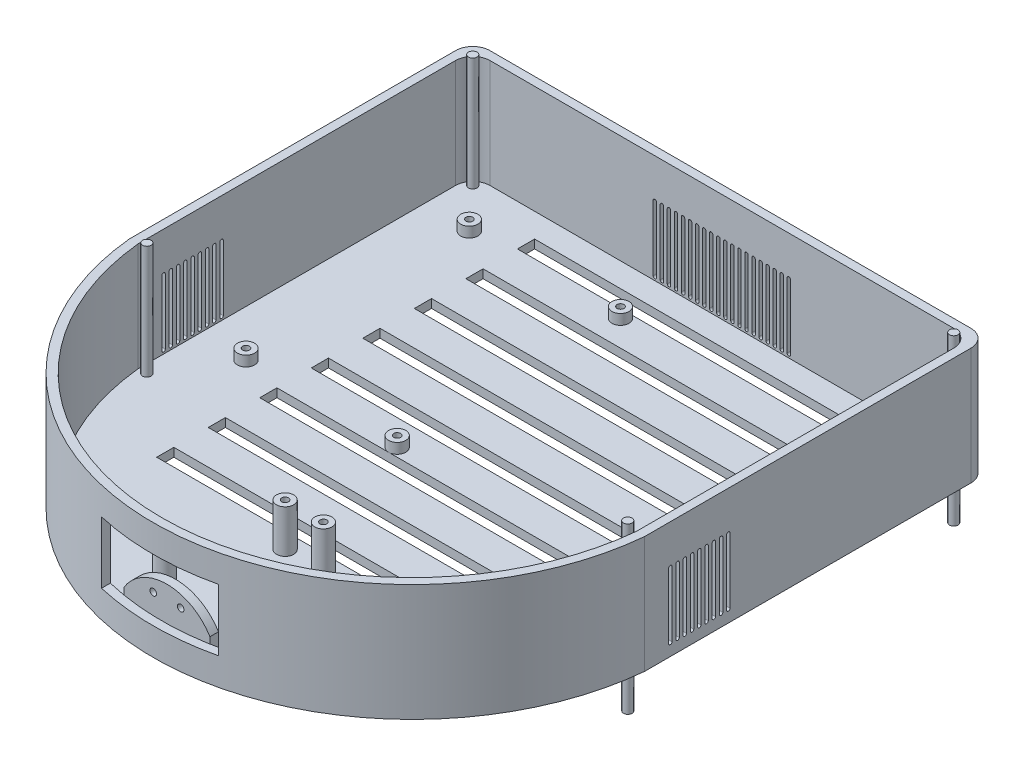
SolidWorks part; units mm, degrees
material "6063-O"
ref_plane "Front Plane" through (0, 0, 0) normal (0, 0, 1) x (1, 0, 0)
ref_plane "Top Plane" through (0, 0, 0) normal (0, 1, 0) x (1, 0, 0)
ref_plane "Right Plane" through (0, 0, 0) normal (1, 0, 0) x (0, 0, -1)
sketch "Sketch1" plane through (0, 0, 0) normal (0, 1, 0) x (1, 0, 0)
  line L1 (-190.5, -213.36) -> (190.5, -213.36)
  line L2 (-190.5, -213.36) -> (-190.5, 213.36)
  line L3 (-190.5, 213.36) -> (190.5, 213.36)
  line L4 (190.5, -213.36) -> (190.5, 213.36)
  line L5 (-190.5, -213.36) -> (190.5, 213.36) construction
  line L6 (-190.5, 213.36) -> (190.5, -213.36) construction
  arc A0 (190.5, -40.64) -> (-190.5, -40.64) centre (0, -21.9449) cw
  point P0 (0, 0)
  dimension "D1" = 381
  dimension "D2" = 426.72
  dimension "D3" = 254
extrude "Boss-Extrude1" add sketch "Sketch1" along normal blind 86.36 contours L4 L3 L2 L1 region at (0, 0, -17.9529)
shell "Shell1" thickness 6.35 removed face at (0, 86.36, -43.18)
fillet "Fillet2" radius 12.7 4 edges at (-190.5, 43.18, -213.36) (190.5, 43.18, -213.36) (184.15, 46.355, -207.01) (-184.15, 46.355, -207.01)
sketch "Sketch3" plane through (0, 6.35, 0) normal (0, 1, 0) x (1, 0, 0)
  line L0 (-177.8, 200.66) -> (-177.8, -40.3265) construction
  circle A2 centre (-177.8, 200.66) radius 7.62
  arc A5 (-177.8, 213.36) -> (-190.5, 200.66) centre (-177.8, 200.66) ccw construction
  circle A6 centre (-177.8, -40.3265) radius 7.62
  circle A8 centre (-177.8, 200.66) radius 3.175
  circle A9 centre (-177.8, -40.3265) radius 3.175
  dimension "D1" = 15.24
  dimension "D2" = 6.35
extrude "Boss-Extrude2" add sketch "Sketch3" against normal blind 38.1 and the other way blind 83.82 contours A9 | A8
mirror "Mirror1" about plane through (0, 0, 0) normal (1, 0, 0) of "Boss-Extrude2"
sketch "Sketch8" plane through (0, 0, -213.36) normal (0, 0, -1) x (-1, 0, 0)
  line L1 (177.8, 0) -> (-177.8, 0) construction
  line L2 (-50.8, 58.42) -> (50.8, 58.42)
  line L3 (-50.8, 58.42) -> (-50.8, 7.62)
  line L4 (-50.8, 7.62) -> (50.8, 7.62)
  line L5 (50.8, 58.42) -> (50.8, 7.62)
  line L6 (-50.8, 58.42) -> (50.8, 7.62) construction
  line L7 (-50.8, 7.62) -> (50.8, 58.42) construction
  line L8 (-49.53, 57.15) -> (-49.53, 8.89) construction
  line L9 (-48.26, 57.15) -> (-48.26, 8.89)
  line L10 (-50.8, 57.15) -> (-50.8, 8.89)
  line L11 (-45.5863, 57.15) -> (-45.5863, 8.89)
  line L12 (-43.0463, 57.15) -> (-43.0463, 8.89)
  line L13 (-44.3163, 57.15) -> (-44.3163, 8.89) construction
  line L14 (-40.3726, 57.15) -> (-40.3726, 8.89)
  line L15 (-37.8326, 57.15) -> (-37.8326, 8.89)
  line L16 (-39.1026, 57.15) -> (-39.1026, 8.89) construction
  line L17 (-35.1589, 57.15) -> (-35.1589, 8.89)
  line L18 (-32.6189, 57.15) -> (-32.6189, 8.89)
  line L19 (-33.8889, 57.15) -> (-33.8889, 8.89) construction
  line L20 (-29.9453, 57.15) -> (-29.9453, 8.89)
  line L21 (-27.4053, 57.15) -> (-27.4053, 8.89)
  line L22 (-28.6753, 57.15) -> (-28.6753, 8.89) construction
  line L23 (-24.7316, 57.15) -> (-24.7316, 8.89)
  line L24 (-22.1916, 57.15) -> (-22.1916, 8.89)
  line L25 (-23.4616, 57.15) -> (-23.4616, 8.89) construction
  line L26 (-19.5179, 57.15) -> (-19.5179, 8.89)
  line L27 (-16.9779, 57.15) -> (-16.9779, 8.89)
  line L28 (-18.2479, 57.15) -> (-18.2479, 8.89) construction
  line L29 (-14.3042, 57.15) -> (-14.3042, 8.89)
  line L30 (-11.7642, 57.15) -> (-11.7642, 8.89)
  line L31 (-13.0342, 57.15) -> (-13.0342, 8.89) construction
  line L32 (-9.0905, 57.15) -> (-9.0905, 8.89)
  line L33 (-6.5505, 57.15) -> (-6.5505, 8.89)
  line L34 (-7.8205, 57.15) -> (-7.8205, 8.89) construction
  line L35 (-3.8768, 57.15) -> (-3.8768, 8.89)
  line L36 (-1.3368, 57.15) -> (-1.3368, 8.89)
  line L37 (-2.6068, 57.15) -> (-2.6068, 8.89) construction
  line L38 (1.3368, 57.15) -> (1.3368, 8.89)
  line L39 (3.8768, 57.15) -> (3.8768, 8.89)
  line L40 (2.6068, 57.15) -> (2.6068, 8.89) construction
  line L41 (6.5505, 57.15) -> (6.5505, 8.89)
  line L42 (9.0905, 57.15) -> (9.0905, 8.89)
  line L43 (7.8205, 57.15) -> (7.8205, 8.89) construction
  line L44 (11.7642, 57.15) -> (11.7642, 8.89)
  line L45 (14.3042, 57.15) -> (14.3042, 8.89)
  line L46 (13.0342, 57.15) -> (13.0342, 8.89) construction
  line L47 (16.9779, 57.15) -> (16.9779, 8.89)
  line L48 (19.5179, 57.15) -> (19.5179, 8.89)
  line L49 (18.2479, 57.15) -> (18.2479, 8.89) construction
  line L50 (22.1916, 57.15) -> (22.1916, 8.89)
  line L51 (24.7316, 57.15) -> (24.7316, 8.89)
  line L52 (23.4616, 57.15) -> (23.4616, 8.89) construction
  line L53 (27.4053, 57.15) -> (27.4053, 8.89)
  line L54 (29.9453, 57.15) -> (29.9453, 8.89)
  line L55 (28.6753, 57.15) -> (28.6753, 8.89) construction
  line L56 (32.6189, 57.15) -> (32.6189, 8.89)
  line L57 (35.1589, 57.15) -> (35.1589, 8.89)
  line L58 (33.8889, 57.15) -> (33.8889, 8.89) construction
  line L59 (37.8326, 57.15) -> (37.8326, 8.89)
  line L60 (40.3726, 57.15) -> (40.3726, 8.89)
  line L61 (39.1026, 57.15) -> (39.1026, 8.89) construction
  line L62 (43.0463, 57.15) -> (43.0463, 8.89)
  line L63 (45.5863, 57.15) -> (45.5863, 8.89)
  line L64 (44.3163, 57.15) -> (44.3163, 8.89) construction
  line L65 (48.26, 57.15) -> (48.26, 8.89)
  line L66 (50.8, 57.15) -> (50.8, 8.89)
  line L67 (49.53, 57.15) -> (49.53, 8.89) construction
  arc A12 (-48.26, 57.15) -> (-50.8, 57.15) centre (-49.53, 57.15) ccw
  arc A13 (-50.8, 8.89) -> (-48.26, 8.89) centre (-49.53, 8.89) ccw
  arc A14 (-43.0463, 57.15) -> (-45.5863, 57.15) centre (-44.3163, 57.15) ccw
  arc A15 (-45.5863, 8.89) -> (-43.0463, 8.89) centre (-44.3163, 8.89) ccw
  arc A16 (-37.8326, 57.15) -> (-40.3726, 57.15) centre (-39.1026, 57.15) ccw
  arc A17 (-40.3726, 8.89) -> (-37.8326, 8.89) centre (-39.1026, 8.89) ccw
  arc A18 (-32.6189, 57.15) -> (-35.1589, 57.15) centre (-33.8889, 57.15) ccw
  arc A19 (-35.1589, 8.89) -> (-32.6189, 8.89) centre (-33.8889, 8.89) ccw
  arc A20 (-27.4053, 57.15) -> (-29.9453, 57.15) centre (-28.6753, 57.15) ccw
  arc A21 (-29.9453, 8.89) -> (-27.4053, 8.89) centre (-28.6753, 8.89) ccw
  arc A22 (-22.1916, 57.15) -> (-24.7316, 57.15) centre (-23.4616, 57.15) ccw
  arc A23 (-24.7316, 8.89) -> (-22.1916, 8.89) centre (-23.4616, 8.89) ccw
  arc A24 (-16.9779, 57.15) -> (-19.5179, 57.15) centre (-18.2479, 57.15) ccw
  arc A25 (-19.5179, 8.89) -> (-16.9779, 8.89) centre (-18.2479, 8.89) ccw
  arc A26 (-11.7642, 57.15) -> (-14.3042, 57.15) centre (-13.0342, 57.15) ccw
  arc A27 (-14.3042, 8.89) -> (-11.7642, 8.89) centre (-13.0342, 8.89) ccw
  arc A28 (-6.5505, 57.15) -> (-9.0905, 57.15) centre (-7.8205, 57.15) ccw
  arc A29 (-9.0905, 8.89) -> (-6.5505, 8.89) centre (-7.8205, 8.89) ccw
  arc A30 (-1.3368, 57.15) -> (-3.8768, 57.15) centre (-2.6068, 57.15) ccw
  arc A31 (-3.8768, 8.89) -> (-1.3368, 8.89) centre (-2.6068, 8.89) ccw
  arc A32 (3.8768, 57.15) -> (1.3368, 57.15) centre (2.6068, 57.15) ccw
  arc A33 (1.3368, 8.89) -> (3.8768, 8.89) centre (2.6068, 8.89) ccw
  arc A34 (9.0905, 57.15) -> (6.5505, 57.15) centre (7.8205, 57.15) ccw
  arc A35 (6.5505, 8.89) -> (9.0905, 8.89) centre (7.8205, 8.89) ccw
  arc A36 (14.3042, 57.15) -> (11.7642, 57.15) centre (13.0342, 57.15) ccw
  arc A37 (11.7642, 8.89) -> (14.3042, 8.89) centre (13.0342, 8.89) ccw
  arc A38 (19.5179, 57.15) -> (16.9779, 57.15) centre (18.2479, 57.15) ccw
  arc A39 (16.9779, 8.89) -> (19.5179, 8.89) centre (18.2479, 8.89) ccw
  arc A40 (24.7316, 57.15) -> (22.1916, 57.15) centre (23.4616, 57.15) ccw
  arc A41 (22.1916, 8.89) -> (24.7316, 8.89) centre (23.4616, 8.89) ccw
  arc A42 (29.9453, 57.15) -> (27.4053, 57.15) centre (28.6753, 57.15) ccw
  arc A43 (27.4053, 8.89) -> (29.9453, 8.89) centre (28.6753, 8.89) ccw
  arc A44 (35.1589, 57.15) -> (32.6189, 57.15) centre (33.8889, 57.15) ccw
  arc A45 (32.6189, 8.89) -> (35.1589, 8.89) centre (33.8889, 8.89) ccw
  arc A46 (40.3726, 57.15) -> (37.8326, 57.15) centre (39.1026, 57.15) ccw
  arc A47 (37.8326, 8.89) -> (40.3726, 8.89) centre (39.1026, 8.89) ccw
  arc A48 (45.5863, 57.15) -> (43.0463, 57.15) centre (44.3163, 57.15) ccw
  arc A49 (43.0463, 8.89) -> (45.5863, 8.89) centre (44.3163, 8.89) ccw
  arc A50 (50.8, 57.15) -> (48.26, 57.15) centre (49.53, 57.15) ccw
  arc A51 (48.26, 8.89) -> (50.8, 8.89) centre (49.53, 8.89) ccw
  point P0 (0, 33.02)
  point P12 (-49.53, 33.02)
  point P21 (-44.3163, 33.02)
  point P28 (-39.1026, 33.02)
  point P36 (-33.8889, 33.02)
  point P43 (-28.6753, 33.02)
  point P50 (-23.4616, 33.02)
  point P57 (-18.2479, 33.02)
  point P64 (-13.0342, 33.02)
  point P71 (-7.8205, 33.02)
  point P78 (-2.6068, 33.02)
  point P85 (2.6068, 33.02)
  point P92 (7.8205, 33.02)
  point P99 (13.0342, 33.02)
  point P106 (18.2479, 33.02)
  point P113 (23.4616, 33.02)
  point P120 (28.6753, 33.02)
  point P127 (33.8889, 33.02)
  point P134 (39.1026, 33.02)
  point P141 (44.3163, 33.02)
  point P148 (49.53, 33.02)
  dimension "D1" = 101.6
  dimension "D2" = 50.8
  dimension "D3" = 7.62
  dimension "D4" = 2.54
  dimension "D5" = 20
extrude "Cut-Extrude4" cut sketch "Sketch8" against normal up to surface (6.35 mm away) contours L10 A13 L9 A12 | L12 A15 L11 A14 | L15 A17 L14 A16 | L18 A19 L17 A18 | L21 A21 L20 A20 | L24 A23 L23 A22 | L27 A25 L26 A24 | L30 A27 L29 A26 | L33 A29 L32 A28 | L36 A31 L35 A30 | L39 A33 L38 A32 | L42 A35 L41 A34 | L45 A37 L44 A36 | L48 A39 L47 A38 | L51 A41 L50 A40 | L54 A43 L53 A42 | L57 A45 L56 A44 | L60 A47 L59 A46 | L63 A49 L62 A48 | L66 A51 L65 A50 up to face at (0, 46.355, -207.01)
sketch "Sketch10" plane through (190.5, 0, 0) normal (1, 0, 0) x (0, 0, -1)
  line L0 (-22.86, 58.42) -> (27.94, 58.42)
  line L1 (-22.86, 58.42) -> (-22.86, 7.62)
  line L2 (-22.86, 7.62) -> (27.94, 7.62)
  line L3 (27.94, 58.42) -> (27.94, 7.62)
  line L4 (-22.86, 58.42) -> (27.94, 7.62) construction
  line L5 (-22.86, 7.62) -> (27.94, 58.42) construction
  line L6 (-40.64, 86.36) -> (-40.64, 0) construction
  line L11 (-40.64, 0) -> (200.66, 0) construction
  line L14 (-21.59, 57.15) -> (-21.59, 8.89) construction
  line L17 (-20.32, 57.15) -> (-20.32, 8.89)
  line L20 (-22.86, 57.15) -> (-22.86, 8.89)
  line L23 (-17.4978, 57.15) -> (-17.4978, 8.89)
  line L26 (-14.9578, 57.15) -> (-14.9578, 8.89)
  line L29 (-16.2278, 57.15) -> (-16.2278, 8.89) construction
  line L32 (-12.1356, 57.15) -> (-12.1356, 8.89)
  line L35 (-9.5956, 57.15) -> (-9.5956, 8.89)
  line L38 (-10.8656, 57.15) -> (-10.8656, 8.89) construction
  line L41 (-6.7733, 57.15) -> (-6.7733, 8.89)
  line L44 (-4.2333, 57.15) -> (-4.2333, 8.89)
  line L47 (-5.5033, 57.15) -> (-5.5033, 8.89) construction
  line L50 (-1.4111, 57.15) -> (-1.4111, 8.89)
  line L53 (1.1289, 57.15) -> (1.1289, 8.89)
  line L56 (-0.1411, 57.15) -> (-0.1411, 8.89) construction
  line L59 (3.9511, 57.15) -> (3.9511, 8.89)
  line L62 (6.4911, 57.15) -> (6.4911, 8.89)
  line L65 (5.2211, 57.15) -> (5.2211, 8.89) construction
  line L66 (9.3133, 57.15) -> (9.3133, 8.89)
  line L67 (11.8533, 57.15) -> (11.8533, 8.89)
  line L68 (10.5833, 57.15) -> (10.5833, 8.89) construction
  line L69 (14.6756, 57.15) -> (14.6756, 8.89)
  line L70 (17.2156, 57.15) -> (17.2156, 8.89)
  line L71 (15.9456, 57.15) -> (15.9456, 8.89) construction
  line L72 (20.0378, 57.15) -> (20.0378, 8.89)
  line L73 (22.5778, 57.15) -> (22.5778, 8.89)
  line L74 (21.3078, 57.15) -> (21.3078, 8.89) construction
  line L75 (25.4, 57.15) -> (25.4, 8.89)
  line L76 (27.94, 57.15) -> (27.94, 8.89)
  line L77 (26.67, 57.15) -> (26.67, 8.89) construction
  arc A40 (-20.32, 57.15) -> (-22.86, 57.15) centre (-21.59, 57.15) ccw
  arc A41 (-22.86, 8.89) -> (-20.32, 8.89) centre (-21.59, 8.89) ccw
  arc A42 (-14.9578, 57.15) -> (-17.4978, 57.15) centre (-16.2278, 57.15) ccw
  arc A43 (-17.4978, 8.89) -> (-14.9578, 8.89) centre (-16.2278, 8.89) ccw
  arc A44 (-9.5956, 57.15) -> (-12.1356, 57.15) centre (-10.8656, 57.15) ccw
  arc A45 (-12.1356, 8.89) -> (-9.5956, 8.89) centre (-10.8656, 8.89) ccw
  arc A46 (-4.2333, 57.15) -> (-6.7733, 57.15) centre (-5.5033, 57.15) ccw
  arc A47 (-6.7733, 8.89) -> (-4.2333, 8.89) centre (-5.5033, 8.89) ccw
  arc A48 (1.1289, 57.15) -> (-1.4111, 57.15) centre (-0.1411, 57.15) ccw
  arc A49 (-1.4111, 8.89) -> (1.1289, 8.89) centre (-0.1411, 8.89) ccw
  arc A50 (6.4911, 57.15) -> (3.9511, 57.15) centre (5.2211, 57.15) ccw
  arc A51 (3.9511, 8.89) -> (6.4911, 8.89) centre (5.2211, 8.89) ccw
  arc A52 (11.8533, 57.15) -> (9.3133, 57.15) centre (10.5833, 57.15) ccw
  arc A53 (9.3133, 8.89) -> (11.8533, 8.89) centre (10.5833, 8.89) ccw
  arc A54 (17.2156, 57.15) -> (14.6756, 57.15) centre (15.9456, 57.15) ccw
  arc A55 (14.6756, 8.89) -> (17.2156, 8.89) centre (15.9456, 8.89) ccw
  arc A56 (22.5778, 57.15) -> (20.0378, 57.15) centre (21.3078, 57.15) ccw
  arc A57 (20.0378, 8.89) -> (22.5778, 8.89) centre (21.3078, 8.89) ccw
  arc A58 (27.94, 57.15) -> (25.4, 57.15) centre (26.67, 57.15) ccw
  arc A59 (25.4, 8.89) -> (27.94, 8.89) centre (26.67, 8.89) ccw
  point P0 (2.54, 33.02)
  point P9 (-21.59, 33.02)
  point P20 (-16.2278, 33.02)
  point P27 (-10.8656, 33.02)
  point P34 (-5.5033, 33.02)
  point P41 (-0.1411, 33.02)
  point P48 (5.2211, 33.02)
  point P55 (10.5833, 33.02)
  point P62 (15.9456, 33.02)
  point P69 (21.3078, 33.02)
  point P76 (26.67, 33.02)
  dimension "D1" = 7.62
  dimension "D2" = 50.8
  dimension "D3" = 50.8
  dimension "D4" = 17.78
  dimension "D5" = 2.54
  dimension "D6" = 10
extrude "Cut-Extrude5" cut sketch "Sketch10" against normal up to surface (6.35 mm away) contours L1 A41 L17 A40 | L23 A43 L26 A42 | L41 A47 L44 A46 | L59 A51 L62 A50 | L66 A53 L67 A52 | L69 A55 L70 A54 | L72 A57 L73 A56 | L32 A45 L35 A44 | L53 A49 L50 A48 region at (190.5, 33.02, 21.59) region at (190.5, 33.02, 16.2278) region at (190.5, 33.02, 5.5033) region at (190.5, 33.02, -5.2211) region at (190.5, 33.02, -10.5833) region at (190.5, 33.02, -15.9456) region at (190.5, 33.02, -21.3078) up to face at (184.15, 46.355, -76.9917)
mirror "Mirror2" about plane through (0, 0, 0) normal (1, 0, 0) of "Cut-Extrude5"
sketch "Sketch11" plane through (0, 6.35, 0) normal (0, 1, 0) x (1, 0, 0)
  line L0 (-171.45, 207.01) -> (171.45, 207.01) construction
  line L1 (-156.21, 176.53) -> (-31.75, 176.53)
  line L2 (-156.21, 176.53) -> (-156.21, -1.27)
  line L3 (-156.21, -1.27) -> (-31.75, -1.27)
  line L4 (-31.75, 176.53) -> (-31.75, -1.27)
  line L5 (-156.21, 176.53) -> (-31.75, -1.27) construction
  line L6 (-156.21, -1.27) -> (-31.75, 176.53) construction
  line L7 (184.15, -40.3265) -> (184.15, 194.31) construction
  circle A0 centre (-149.86, 170.18) radius 6.35
  circle A1 centre (-149.86, 5.08) radius 6.35
  circle A2 centre (-149.86, 170.18) radius 2.54
  circle A3 centre (-149.86, 5.08) radius 2.54
  circle A4 centre (-38.1, 170.18) radius 6.35
  circle A5 centre (-38.1, 170.18) radius 2.54
  circle A6 centre (-38.1, 5.08) radius 6.35
  circle A7 centre (-38.1, 5.08) radius 2.54
  point P0 (-93.98, 87.63)
  dimension "D4" = 12.7
  dimension "D5" = 5.08
  dimension "D1" = 124.46
  dimension "D2" = 177.8
  dimension "D3" = 30.48
  dimension "D6" = 215.9
extrude "Boss-Extrude3" add sketch "Sketch11" along normal blind 7.62 contours A0 A2 | A1 A3 | A4 | A6 | A7 | A5 region at (-145.4969, 6.35, -174.5431) region at (-149.86, 6.35, -11.2504)
sketch "Sketch12" plane through (0, 6.35, 0) normal (0, 1, 0) x (1, 0, 0)
  line L0 (-171.45, 207.01) -> (171.45, 207.01) construction
  line L5 (120.65, 189.23) -> (-120.65, 189.23)
  line L6 (120.65, 189.23) -> (120.65, 176.53)
  line L7 (120.65, 176.53) -> (-120.65, 176.53)
  line L8 (-120.65, 189.23) -> (-120.65, 176.53)
  line L9 (120.65, 189.23) -> (-120.65, 176.53) construction
  line L10 (120.65, 176.53) -> (-120.65, 189.23) construction
  point P0 (0, 182.88)
  dimension "D1" = 12.7
  dimension "D2" = 241.3
  dimension "D3" = 17.78
extrude "Cut-Extrude6" cut sketch "Sketch12" against normal up to surface (6.35 mm away) up to face at (177.8, 0, -197.485)
pattern_linear "LPattern1" count 8 spacing 38.1 along (0, 0, 1) of "Cut-Extrude6"
ref_plane "Plane1" through (0, 0, 213.36) normal (0, 0, -1) x (-1, 0, 0)
sketch "Sketch13" plane through (0, 0, 213.36) normal (0, 0, -1) x (-1, 0, 0)
  line L1 (43.18, 66.04) -> (-43.18, 66.04)
  line L2 (43.18, 66.04) -> (43.18, 20.32)
  line L3 (43.18, 20.32) -> (-43.18, 20.32)
  line L4 (-43.18, 66.04) -> (-43.18, 20.32)
  line L5 (43.18, 66.04) -> (-43.18, 20.32) construction
  line L6 (43.18, 20.32) -> (-43.18, 66.04) construction
  line L8 (-190.5, 86.36) -> (-190.5, 0) construction
  point P0 (0, 43.18)
  point P14 (-190.5, 43.18)
  dimension "D1" = 86.36
  dimension "D2" = 45.72
extrude "Cut-Extrude7" cut sketch "Sketch13" along normal up to surface (11.4579 mm away) up to face at (0, 46.355, 123.6683)
sketch "Sketch14" plane through (0, 6.35, 0) normal (0, 1, 0) x (1, 0, 0)
  line L1 (-31.75, -196.85) -> (31.75, -196.85)
  line L2 (-31.75, -196.85) -> (-31.75, -203.2)
  line L3 (-31.75, -203.2) -> (31.75, -203.2)
  line L4 (31.75, -196.85) -> (31.75, -203.2)
  line L5 (-31.75, -196.85) -> (31.75, -203.2) construction
  line L6 (-31.75, -203.2) -> (31.75, -196.85) construction
  point P0 (0, -200.025)
  dimension "D1" = 6.35
  dimension "D2" = 63.5
  dimension "D3" = 196.85
extrude "Boss-Extrude4" add sketch "Sketch14" along normal blind 35.56
sketch "Sketch15" plane through (0, 0, 203.2) normal (0, 0, 1) x (1, 0, 0)
  line L1 (-31.75, 41.91) -> (31.75, 41.91) construction
  line L2 (-31.75, 41.91) -> (-31.75, 6.35) construction
  line L3 (-31.75, 24.13) -> (-31.75, 6.35)
  line L4 (-31.75, 6.35) -> (31.75, 6.35)
  line L5 (31.75, 6.35) -> (31.75, 24.13)
  line L6 (10.16, 31.75) -> (-10.16, 31.75) construction
  line L7 (-31.75, 24.13) -> (-31.75, 41.91)
  line L8 (-31.75, 41.91) -> (31.75, 41.91)
  line L9 (31.75, 41.91) -> (31.75, 24.13)
  arc A0 (-31.75, 24.13) -> (31.75, 24.13) centre (0, 4.6718) cw
  circle A1 centre (-10.16, 31.75) radius 2.413
  circle A2 centre (10.16, 31.75) radius 2.413
  point P11 (0, 31.75)
  line M6 (31.75, 6.35) -> (31.75, 41.91)
  line M7 (31.75, 41.91) -> (-31.75, 41.91)
  line M8 (-31.75, 41.91) -> (-31.75, 6.35)
  dimension "D1" = 4.826
  dimension "D2" = 20.32
  dimension "D3" = 25.4
extrude "Cut-Extrude8" cut sketch "Sketch15" against normal up to surface (6.35 mm away) contours A0 L8 M8 | A0 M7 M6 | A2 | A1 region at (-24.2403, 36.898, 203.2) region at (24.2403, 36.898, 203.2) region at (-10.16, 31.75, 203.2) region at (10.16, 31.75, 203.2) up to face at (0, 24.13, 196.85)
sketch "Sketch17" plane through (0, 6.35, 0) normal (0, 1, 0) x (1, 0, 0)
  line L5 (38.1, -179.578) -> (-38.1, -179.578)
  line L6 (38.1, -179.578) -> (38.1, -66.04)
  line L8 (38.1, -66.04) -> (-38.1, -66.04)
  line L9 (-38.1, -179.578) -> (-38.1, -66.04)
  line L10 (38.1, -179.578) -> (-38.1, -66.04) construction
  line L11 (38.1, -66.04) -> (-38.1, -179.578) construction
  line L13 (-177.8, 213.36) -> (177.8, 213.36) construction
  circle A9 centre (-14.1546, -101.7186) radius 2.54
  circle A10 centre (14.1546, -101.7186) radius 2.54
  circle A11 centre (-31.75, -173.228) radius 2.54
  circle A12 centre (31.75, -173.228) radius 2.54
  circle A13 centre (31.75, -173.228) radius 6.35
  circle A14 centre (-31.75, -173.228) radius 6.35
  circle A15 centre (14.1546, -101.7186) radius 6.35
  circle A16 centre (-14.1546, -101.7186) radius 6.35
  point P0 (0, -122.809)
  dimension "D4" = 279.4
  dimension "D5" = 76.2
  dimension "D1" = 5.08
  dimension "D6" = 113.538
  dimension "D2" = 12.7
  dimension "D3" = 12.7
  dimension "D7" = 25.4
  dimension "D8" = 25.4
extrude "Boss-Extrude5" add sketch "Sketch17" along normal blind 31.75 contours A14 A11 | A16 A9 | A15 A10 | A12 | A13 region at (-36.1131, 6.35, 177.5911) region at (7.9843, 6.35, 101.7186) region at (-20.325, 6.35, 101.7186)
